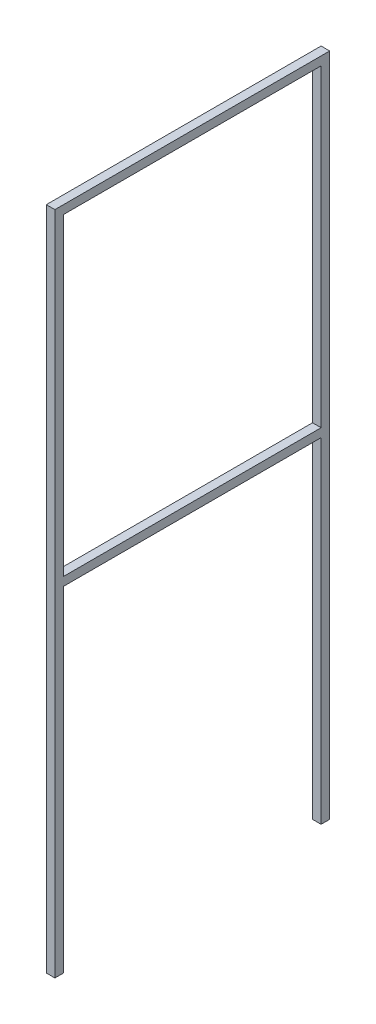
SolidWorks part; units mm, degrees
ref_plane "Front" through (0, 0, 0) normal (0, 0, 1) x (1, 0, 0)
ref_plane "Top" through (0, 0, 0) normal (0, 1, 0) x (1, 0, 0)
ref_plane "Right" through (0, 0, 0) normal (1, 0, 0) x (0, 0, -1)
sketch "Sketch1" plane through (0, 0, 0) normal (1, 0, 0) x (0, 0, -1)
  line L0 (0, 0) -> (0, -500)
  line L1 (0, -500) -> (-600, -500)
  line L2 (-600, -520) -> (-600, -650)
  line L3 (0, -520) -> (0, -650)
  line L4 (-600, -500) -> (-600, 0)
  line L5 (-600, -650) -> (-600, -670)
  line L6 (20, 0) -> (20, -500)
  line L7 (0, -520) -> (-600, -520)
  line L8 (-620, -500) -> (-620, 0)
  line L9 (20, -500) -> (20, -1300)
  line L10 (-620, -500) -> (-620, -1300)
  line L11 (0, -650) -> (0, -670)
  line L12 (-600, 230) -> (0, 230)
  line L13 (-600, 250) -> (0, 250)
  line L14 (20, -1300) -> (0, -1300)
  line L15 (-600, -1300) -> (-620, -1300)
  line L16 (0, -500) -> (0, -1300) construction
  line L17 (0, -670) -> (0, -1300)
  line L18 (-600, -670) -> (-600, -1300)
  line L19 (-600, -500) -> (-600, -1300) construction
  line L20 (20, 0) -> (20, 250)
  line L21 (0, 0) -> (0, 230)
  line L22 (-600, 230) -> (-600, 0)
  line L23 (-620, 250) -> (-620, 0)
  line L24 (-620, 250) -> (-600, 250)
  line L25 (0, 250) -> (20, 250)
  dimension "D1" = 500
  dimension "D2" = 800
  dimension "D3" = 20
  dimension "D5" = 20
  dimension "D6" = 20
extrude "Boss-Extrude1" add sketch "Sketch1" along normal blind 20 contours L18 L17 L14 L9 L6 L0 L1 L4 L8 L10 L15 L7 L3 L2 region at (0, -585, 616.7693)
